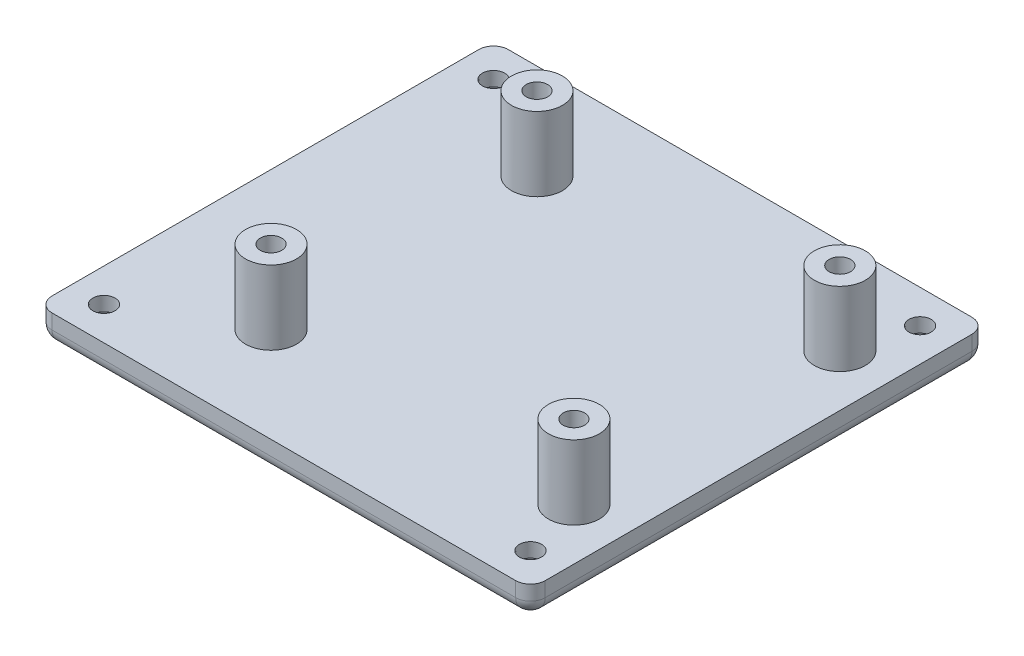
SolidWorks part; units mm, degrees
ref_plane "Front Plane" through (0, 0, 0) normal (0, 0, 1) x (1, 0, 0)
ref_plane "Top Plane" through (0, 0, 0) normal (0, 1, 0) x (1, 0, 0)
ref_plane "Right Plane" through (0, 0, 0) normal (1, 0, 0) x (0, 0, -1)
sketch "Sketch1" plane through (0, 0, 0) normal (0, 1, 0) x (1, 0, 0)
  line L1 (0, 0) -> (66.76, 0)
  line L2 (0, 0) -> (0, 61.76)
  line L3 (0, 61.76) -> (66.76, 61.76)
  line L4 (66.76, 0) -> (66.76, 61.76)
  dimension "D1" = 66.76
  dimension "D2" = 61.76
extrude "Boss-Extrude3" add sketch "Sketch1" against normal blind 4
sketch "Sketch2" plane through (0, 0, 0) normal (0, 1, 0) x (1, 0, 0)
  line L0 (63.76, 8.88) -> (14.76, 8.88) construction
  line L1 (0, 61.76) -> (0, 0) construction
  line L2 (18.76, 12.88) -> (59.76, 12.88) construction
  line L3 (0, 0) -> (66.76, 0) construction
  line L4 (66.76, 0) -> (66.76, 61.76) construction
  line L5 (66.76, 61.76) -> (0, 61.76) construction
  line L6 (63.76, 59.75) -> (63.76, 2.01) construction
  line L7 (2.01, 2.01) -> (64.75, 2.01) construction
  line L8 (2.01, 2.01) -> (2.01, 59.75) construction
  line L9 (2.01, 59.75) -> (64.75, 59.75) construction
  line L10 (64.75, 2.01) -> (64.75, 59.75) construction
  line L11 (18.76, 12.88) -> (18.76, 48.88) construction
  line L12 (18.76, 48.88) -> (59.76, 48.88) construction
  line L13 (59.76, 12.88) -> (59.76, 48.88) construction
  line L14 (14.76, 8.88) -> (14.76, 52.88) construction
  line L15 (14.76, 52.88) -> (63.76, 52.88) construction
  line L16 (0, 30.88) -> (66.76, 30.88) construction
  line L17 (39.26, 12.88) -> (39.26, 48.88) construction
  circle A0 centre (59.76, 12.88) radius 1.45
  circle A4 centre (59.76, 12.88) radius 3.45
  circle A5 centre (18.76, 12.88) radius 3.45
  circle A6 centre (18.76, 12.88) radius 1.45
  circle A7 centre (18.76, 48.88) radius 1.45
  circle A8 centre (59.76, 48.88) radius 1.45
  circle A9 centre (59.76, 48.88) radius 3.45
  circle A10 centre (18.76, 48.88) radius 3.45
  dimension "D13" = 2.9
  dimension "D11" = 6.9
  dimension "D1" = 2.01
  dimension "D2" = 2.01
  dimension "D3" = 0.99
  dimension "D4" = 2.01
  dimension "D5" = 2.01
  dimension "D6" = 49
  dimension "D7" = 44
  dimension "D8" = 22
  dimension "D9" = 4
  dimension "D10" = 4
  dimension "D12" = 4
extrude "Boss-Extrude4" add sketch "Sketch2" along normal blind 10
sketch "Sketch3" plane through (0, 0, 0) normal (0, 1, 0) x (1, 0, 0)
  line L0 (0, 61.76) -> (0, 0) construction
  line L1 (33.38, 59.75) -> (33.38, 2.01) construction
  line L2 (2.01, 30.88) -> (64.75, 30.88) construction
  line L3 (2.01, 59.75) -> (64.75, 59.75) construction
  line L6 (2.01, 59.75) -> (2.01, 2.01) construction
  line L11 (2.01, 2.01) -> (64.75, 2.01) construction
  line L12 (64.75, 59.75) -> (64.75, 2.01) construction
  line L13 (0, 0) -> (66.76, 0) construction
  line L14 (66.76, 61.76) -> (0, 61.76) construction
  line L15 (66.76, 0) -> (66.76, 61.76) construction
  circle A0 centre (4.51, 57.25) radius 1.5
  circle A1 centre (62.25, 57.25) radius 1.5
  circle A2 centre (62.25, 4.51) radius 1.5
  circle A3 centre (4.51, 4.51) radius 1.5
  dimension "D5" = 3
  dimension "D1" = 2.01
  dimension "D2" = 2.01
  dimension "D3" = 2.01
  dimension "D4" = 2.01
  dimension "D6" = 2.5
  dimension "D7" = 2.5
extrude "Cut-Extrude1" cut sketch "Sketch3" against normal blind 3 draft 3 draft outward yes
sketch "Sketch5" plane through (0, -4, 0) normal (0, -1, 0) x (1, 0, 0)
  line L0 (33.38, -4.51) -> (33.38, -57.6662) construction
  line L1 (4.51, -4.51) -> (62.25, -4.51) construction
  line L2 (4.51, -4.51) -> (4.51, -57.25) construction
  line L3 (4.51, -57.25) -> (62.25, -57.25) construction
  line L4 (62.25, -4.51) -> (62.25, -57.25) construction
  line L5 (4.51, -30.88) -> (62.25, -30.88) construction
  circle A0 centre (4.51, -4.51) radius 3
  circle A1 centre (62.25, -4.51) radius 3
  circle A2 centre (62.25, -57.25) radius 3
  circle A3 centre (4.51, -57.25) radius 3
  point P10 (33.38, -30.88)
  dimension "D1" = 6
fillet "Fillet2" radius 2 4 edges at (0, -2, 0) (66.76, -2, 0) (66.76, -2, -61.76) (0, -2, -61.76)
fillet "Fillet1" radius 2 8 edges at (66.76, -4, -30.88) (33.38, -4, -61.76) (0, -4, -30.88) (33.38, -4, 0) (0.5858, -4, -0.5858) (0.5858, -4, -61.1742) (66.1742, -4, -61.1742) (66.1742, -4, -0.5858)
extrude "Cut-Extrude2" cut sketch "Sketch5" against normal blind 2 draft 1
